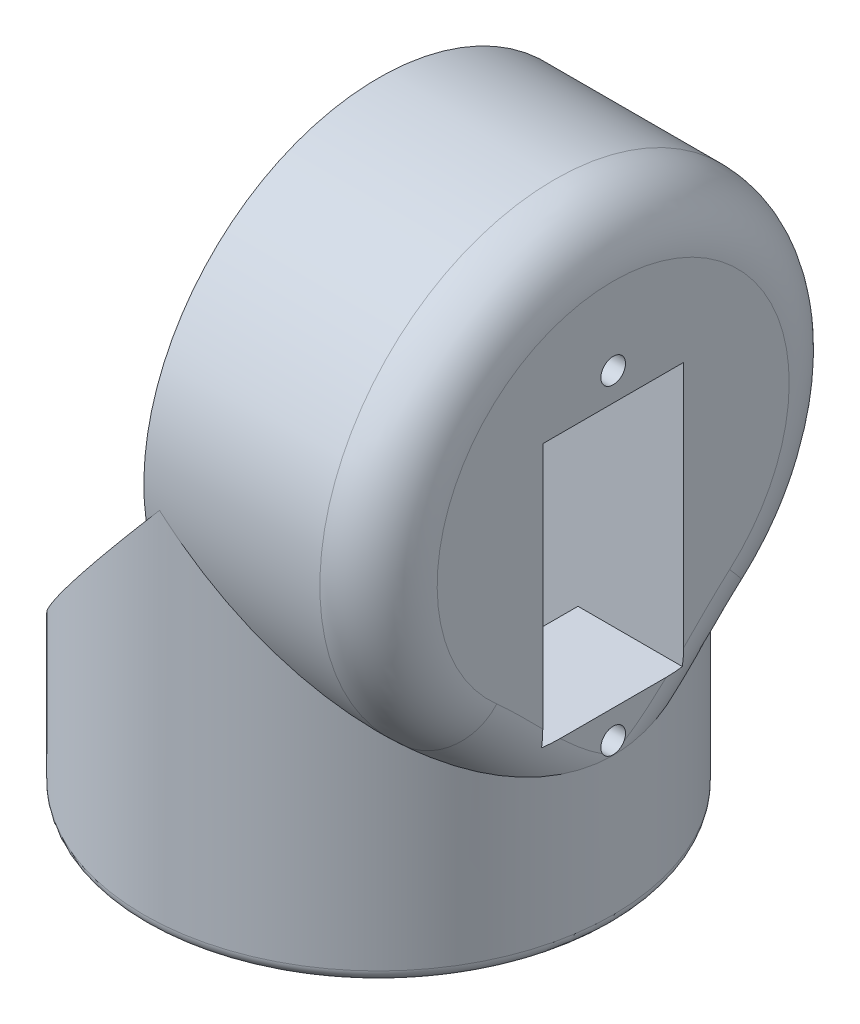
SolidWorks part; units mm, degrees
material "ABS"
ref_plane "Front Plane" through (0, 0, 0) normal (0, 0, 1) x (1, 0, 0)
ref_plane "Top Plane" through (0, 0, 0) normal (0, 1, 0) x (1, 0, 0)
ref_plane "Right Plane" through (0, 0, 0) normal (1, 0, 0) x (0, 0, -1)
sketch "Sketch1" plane through (0, 0, 0) normal (0, 1, 0) x (1, 0, 0)
  circle A0 centre (0, 0) radius 20
  dimension "D1" = 40
extrude "Boss-Extrude1" add sketch "Sketch1" along normal blind 4
sketch "Sketch2" plane through (0, 0, 0) normal (0, -1, 0) x (1, 0, 0)
  circle A0 centre (0, 0) radius 10.5
  dimension "D1" = 21
extrude "Cut-Extrude1" cut sketch "Sketch2" against normal blind 2
sketch "Sketch3" plane through (0, 2, 0) normal (0, -1, 0) x (1, 0, 0)
  circle A0 centre (0, 0) radius 1
  dimension "D1" = 2
extrude "Cut-Extrude2" cut sketch "Sketch3" against normal blind 12
sketch "Sketch4" plane through (0, 0, 0) normal (0, -1, 0) x (1, 0, 0)
  point P0 (0, 0)
fillet "Fillet1" radius 1 1 edges at (0, 0, 20)
fillet "Fillet2" radius 0.5 1 edges at (0, 0, -10.5)
sketch "Sketch5" plane through (0, 4, 0) normal (0, 1, 0) x (1, 0, 0)
  circle A0 centre (-15.1019, 0) radius 3.25
  dimension "D1" = 6.5
extrude "Cut-Extrude3" cut sketch "Sketch5" against normal blind 12
sketch "Sketch6" plane through (0, 4, 0) normal (0, 1, 0) x (1, 0, 0)
  circle A0 centre (0, 0) radius 20
  circle A1 centre (0, 0) radius 18.5
  dimension "D1" = 37
extrude "Boss-Extrude2" add sketch "Sketch6" along normal blind 40
sketch "Sketch7" plane through (0, 0, 0) normal (0, 0, 1) x (1, 0, 0)
  line L1 (18.5, 44) -> (-18.5, 44) construction
  line L2 (-20, 44) -> (-20, 6.4228)
  line L3 (-20, 44) -> (-20, 1) construction
  line L4 (-20, 6.4228) -> (11.9315, 44)
  line L6 (-20, 44) -> (11.9315, 44)
extrude "Cut-Extrude4" cut sketch "Sketch7" against normal mid plane 60
sketch "Sketch8" plane through (0, 0, 0) normal (1, 0, 0) x (0, 0, -1)
  line L0 (16.0512, 44) -> (-16.0512, 44) construction
  line L1 (-7.9543, 6.7612) -> (7.9543, 6.7612)
  line L2 (-7.9543, 6.7612) -> (-7.9543, 44)
  line L3 (-7.9543, 44) -> (7.9543, 44)
  line L4 (7.9543, 6.7612) -> (7.9543, 44)
  line L5 (-7.9543, 6.7612) -> (7.9543, 44) construction
  line L6 (-7.9543, 44) -> (7.9543, 6.7612) construction
  point P0 (0, 25.3806)
extrude "Boss-Extrude3" add sketch "Sketch8" along normal up to surface (16.7027 mm away) up to face at (0, 26.094, 0)
sketch "Sketch9" plane through (0, 0, 0) normal (-1, 0, 0) x (0, 0, 1)
  line L1 (7.9543, 44) -> (-7.9543, 44)
  line L2 (7.9543, 44) -> (7.9543, 6.7612)
  line L3 (7.9543, 6.7612) -> (-7.9543, 6.7612)
  line L4 (-7.9543, 44) -> (-7.9543, 6.7612)
extrude "Boss-Extrude4" add sketch "Sketch9" against normal blind 20
sketch "Sketch10" plane through (20, 0, 0) normal (1, 0, 0) x (0, 0, -1)
  circle A0 centre (0, 25.3806) radius 18.6194
extrude "Boss-Extrude5" add sketch "Sketch10" against normal blind 20
sketch "Sketch11" plane through (0, 0, 0) normal (-1, 0, 0) x (0, 0, 1)
  line L0 (-7.9543, 44) -> (7.9543, 44) construction
  line L1 (-6, 11) -> (6, 11)
  line L2 (-6, 11) -> (-6, 44)
  line L3 (-6, 44) -> (6, 44)
  line L4 (6, 11) -> (6, 44)
  line L5 (-6, 11) -> (6, 44) construction
  line L6 (-6, 44) -> (6, 11) construction
  point P0 (0, 27.5)
  dimension "D1" = 33
  dimension "D2" = 12
  dimension "D3" = 6
extrude "Cut-Extrude5" cut sketch "Sketch11" against normal blind 11
fillet "Fillet3" radius 0.5 6 edges at (0, 11, 0) (11, 44, 0) (5.5, 44, 6) (5.5, 44, -6) (0, 27.5, -6) (0, 27.5, 6)
sketch "Sketch12" plane through (11, 0, 0) normal (-1, 0, 0) x (0, 0, 1)
  line L0 (-6, 43.5) -> (-6, 11) construction
  line L1 (-6, 38.7748) -> (6, 38.7748)
  line L2 (-6, 38.7748) -> (-6, 16.2748)
  line L3 (-6, 16.2748) -> (6, 16.2748)
  line L4 (6, 38.7748) -> (6, 16.2748)
  line L5 (6, 11) -> (6, 43.5) construction
  circle A0 centre (0, 41.1748) radius 1.05
  circle A1 centre (0, 13.8748) radius 1.05
  point P12 (0, 32.7748)
  dimension "D2" = 2.1
  dimension "D3" = 2.1
  dimension "D1" = 22.5
  dimension "D4" = 8.4
  dimension "D5" = 6
  dimension "D6" = 18.9
extrude "Cut-Extrude6" cut sketch "Sketch12" against normal blind 11
sketch "Sketch13" plane through (20, 0, 0) normal (1, 0, 0) x (0, 0, -1)
  point P0 (0, 32.7748)
sketch "Sketch14" plane through (20, 0, 0) normal (1, 0, 0) x (0, 0, -1)
  line L1 (-10.4419, 28.6552) -> (-18.6044, 25.4349)
  line L2 (10.4278, 28.6196) -> (18.5793, 25.3715)
  arc A0 (18.5793, 25.3715) -> (-18.6044, 25.4349) centre (0, 32.7748) ccw
  arc A1 (10.4278, 28.6196) -> (-10.4419, 28.6552) centre (0, 32.7748) ccw
  dimension "D1" = 40
extrude "Boss-Extrude6" add sketch "Sketch14" against normal blind 20
fillet "Fillet4" radius 0.5 1 edges at (13.6512, 25.4724, 18.6192)
sketch "Sketch15" plane through (20, 0, 0) normal (1, 0, 0) x (0, 0, -1)
  line L4 (-7.9543, 8.5457) -> (-7.9543, 6.7612)
  line L5 (-7.9543, 6.7612) -> (0, 6.7612)
  line L6 (0, 6.7612) -> (7.9543, 6.7612)
  line L7 (7.9543, 6.7612) -> (7.9543, 8.5457)
  line L8 (-7.9543, 8.5457) -> (-7.9543, 6.7612)
  line L9 (-7.9543, 6.7612) -> (0, 6.7612)
  line L10 (0, 6.7612) -> (7.9543, 6.7612)
  line L11 (7.9543, 6.7612) -> (7.9543, 8.5457)
  arc A0 (-18.6531, 25.5594) -> (18.6192, 25.4724) centre (0, 32.7748) ccw
  arc A5 (7.9543, 8.5457) -> (18.6192, 25.4724) centre (0, 25.3806) ccw
  arc A6 (18.6192, 25.4724) -> (-18.6531, 25.5594) centre (0, 32.7748) ccw
  arc A7 (-18.6194, 25.3791) -> (-18.6531, 25.5594) centre (-19.1194, 25.379) ccw
  arc A8 (-18.6194, 25.3791) -> (-7.9543, 8.5457) centre (0, 25.3806) ccw
  arc A9 (7.9543, 8.5457) -> (18.6192, 25.4724) centre (0, 25.3806) ccw
  arc A11 (-18.6194, 25.3791) -> (-18.6531, 25.5594) centre (-19.1194, 25.379) ccw
  arc A12 (-18.6194, 25.3791) -> (-7.9543, 8.5457) centre (0, 25.3806) ccw
  dimension "D1" = 0
extrude "Cut-Extrude7" cut sketch "Sketch15" against normal up to surface (1.6498 mm away) up to face at (0, 1, 20)
sketch "Sketch16" plane through (0, 0, 0) normal (-1, 0, 0) x (0, 0, 1)
  line L7 (6.5, 10.5) -> (-6.5, 10.5) construction
  line L8 (6.5, 41.9266) -> (6.5, 10.5) construction
  line L9 (-6.5, 10.5) -> (-6.5, 41.9266) construction
  line L10 (6.5, 10.5) -> (-6.5, 10.5)
  line L11 (6.5, 41.9266) -> (6.5, 10.5)
  line L12 (-6.5, 10.5) -> (-6.5, 41.9266)
  line L14 (16.5, 23.3919) -> (16.5, 31.959)
  line L15 (16.5, 31.959) -> (17.9815, 31.959)
  line L16 (-17.9815, 31.959) -> (-16.5, 31.959)
  line L17 (-16.5, 31.959) -> (-16.5, 23.3919)
  line L18 (-5.9543, 9.8644) -> (-5.9543, 8.7612)
  line L19 (-5.9543, 8.7612) -> (5.9543, 8.7612)
  line L20 (5.9543, 8.7612) -> (5.9543, 9.8644)
  line L21 (16.5, 23.3919) -> (16.5, 31.959)
  line L22 (16.5, 31.959) -> (17.9815, 31.959)
  line L23 (-17.9815, 31.959) -> (-16.5, 31.959)
  line L24 (-16.5, 31.959) -> (-16.5, 23.3919)
  line L25 (-5.9543, 9.8644) -> (-5.9543, 8.7612)
  line L26 (-5.9543, 8.7612) -> (5.9543, 8.7612)
  line L27 (5.9543, 8.7612) -> (5.9543, 9.8644)
  arc A3 (6.5, 41.9266) -> (-6.5, 41.9266) centre (0, 32.7748) ccw construction
  arc A4 (6.5, 41.9266) -> (-6.5, 41.9266) centre (0, 32.7748) ccw
  arc A6 (5.9543, 9.8644) -> (16.5, 23.3919) centre (0, 25.3806) ccw
  arc A7 (17.9815, 31.959) -> (-17.9815, 31.959) centre (0, 32.7748) ccw
  arc A8 (-16.5, 23.3919) -> (-5.9543, 9.8644) centre (0, 25.3806) ccw
  arc A9 (5.9543, 9.8644) -> (16.5, 23.3919) centre (0, 25.3806) ccw
  arc A10 (17.9815, 31.959) -> (-17.9815, 31.959) centre (0, 32.7748) ccw
  arc A11 (-16.5, 23.3919) -> (-5.9543, 9.8644) centre (0, 25.3806) ccw
  dimension "D1" = 2
extrude "Cut-Extrude8" cut sketch "Sketch16" against normal up to surface (17.3205 mm away) up to face at (0, 4, 18.5)
sketch "Sketch17" plane through (0, 4, 0) normal (0, 1, 0) x (1, 0, 0)
  circle A0 centre (0, 0) radius 3.0756
extrude "Cut-Extrude9" cut sketch "Sketch17" along normal blind 20
sketch "Sketch19" plane through (0, 0, -6) normal (0, 0, 1) x (1, 0, 0)
  line L0 (11, 38.7748) -> (11, 42.2619)
  line L3 (11, 42.2619) -> (-2.0671, 42.2619)
  line L4 (-2.0671, 42.2619) -> (-2.0671, 11.5821)
  line L5 (-2.0671, 11.5821) -> (-2.0671, 10.7911)
  line L6 (-2.0671, 10.7911) -> (0.5, 11)
  arc A0 (0.5, 11) -> (11, 38.7748) centre (56.5704, 5.6753) cw
extrude "Cut-Extrude11" cut sketch "Sketch19" against normal blind 1 and the other way blind 13
sketch "Sketch20" plane through (11, 0, 0) normal (-1, 0, 0) x (0, 0, 1)
  line L1 (8.3309, 6.3394) -> (-7.9332, 6.3394)
  line L2 (8.3309, 6.3394) -> (8.3309, 11.2124)
  line L3 (8.3309, 11.2124) -> (-7.9332, 11.2124)
  line L4 (-7.9332, 6.3394) -> (-7.9332, 11.2124)
extrude "Boss-Extrude7" add sketch "Sketch20" along normal blind 9 and the other way blind 7
fillet "Fillet5" radius 0.5 1 edges at (11, 42.8402, -4.9691)
fillet "Fillet6" radius 0.5 1 edges at (11, 42.8402, 4.9691)
sketch "Sketch21" plane through (0, 4, 0) normal (0, 1, 0) x (1, 0, 0)
  circle A1 centre (0, 0) radius 18.5
  circle A2 centre (0, 0) radius 18.5
  dimension "D1" = 0
extrude "Boss-Extrude8" add sketch "Sketch21" along normal blind 3
sketch "Sketch22" plane through (0, 4, 0) normal (0, -1, 0) x (1, 0, 0)
  circle A0 centre (0, 0) radius 1
  circle A1 centre (-15.1019, 0) radius 3.25
extrude "Cut-Extrude12" cut sketch "Sketch22" against normal blind 13
sketch "Sketch23" plane through (20, 0, 0) normal (1, 0, 0) x (0, 0, -1)
  line L0 (6, 16.2748) -> (6, 38.7748) construction
  line L1 (-6, 16.2748) -> (6, 16.2748) construction
  line L2 (-6, 38.7748) -> (-6, 16.2748) construction
  line L3 (6, 38.7748) -> (-6, 38.7748) construction
  line L4 (6, 16.2748) -> (6, 38.7748)
  line L5 (-6, 16.2748) -> (6, 16.2748)
  line L6 (-6, 38.7748) -> (-6, 16.2748)
  line L7 (6, 38.7748) -> (-6, 38.7748)
  circle A0 centre (0, 13.8748) radius 1.05 construction
  circle A1 centre (0, 32.7748) radius 20
  circle A2 centre (0, 32.7748) radius 20
  circle A3 centre (0, 41.1748) radius 1.05 construction
  circle A4 centre (0, 13.8748) radius 1.05
  circle A5 centre (0, 41.1748) radius 1.05
  dimension "D1" = 0
extrude "Boss-Extrude9" add sketch "Sketch23" against normal blind 4
sketch "Sketch24" plane through (0, 7, 0) normal (0, 1, 0) x (1, 0, 0)
  circle A0 centre (-15.1019, 0) radius 3.25
extrude "Boss-Extrude10" add sketch "Sketch24" against normal blind 7
sketch "Sketch25" plane through (0, 7, 0) normal (0, 1, 0) x (1, 0, 0)
  circle A0 centre (0, 0) radius 2.5
  dimension "D1" = 5
extrude "Cut-Extrude13" cut sketch "Sketch25" against normal blind 2
fillet "Fillet7" radius 5 1 edges at (20, 32.7748, -20)
